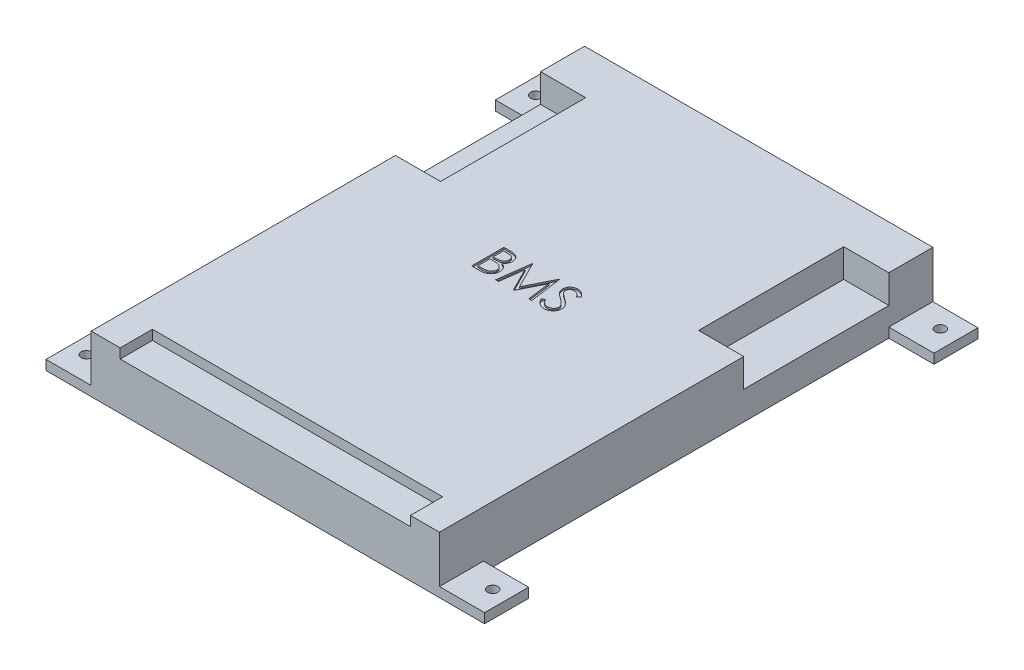
SolidWorks part; units mm, degrees
ref_plane "Front Plane" through (0, 0, 0) normal (0, 0, 1) x (1, 0, 0)
ref_plane "Top Plane" through (0, 0, 0) normal (0, 1, 0) x (1, 0, 0)
ref_plane "Right Plane" through (0, 0, 0) normal (1, 0, 0) x (0, 0, -1)
sketch "Sketch1" plane through (0, 0, 0) normal (0, 1, 0) x (1, 0, 0)
  line L0 (0, 0) -> (0, 13.65)
  line L5 (0, 13.65) -> (14, 13.65)
  line L6 (14, 13.65) -> (14, 139.35)
  line L7 (14, 139.35) -> (0, 139.35)
  line L8 (0, 139.35) -> (0, 153)
  line L9 (0, 153) -> (136, 153)
  line L10 (68, 153) -> (68, 0) construction
  line L11 (136, 0) -> (0, 0)
  line L12 (136, 139.35) -> (136, 153)
  line L13 (122, 139.35) -> (136, 139.35)
  line L14 (122, 13.65) -> (122, 139.35)
  line L15 (136, 13.65) -> (122, 13.65)
  line L16 (136, 0) -> (136, 13.65)
  line L17 (14, 76.5) -> (122, 76.5) construction
  point P18 (5, 146.85)
  point P19 (5, 7.5)
  point P20 (0, 0)
  point P21 (131, 7.5)
  point P22 (131, 146.85)
  point P23 (0, 0)
  point P24 (23.8963, 7.5)
  point P25 (0, 0)
  dimension "D1" = 153
  dimension "D2" = 125.7
  dimension "D3" = 136
  dimension "D4" = 108
  dimension "D5" = 70.35
  dimension "D6" = 126
  dimension "D7" = 139.35
extrude "Boss-Extrude1" add sketch "Sketch1" along normal blind 3
sketch "Sketch3" plane through (0, 3, 0) normal (0, 1, 0) x (1, 0, 0)
  line L0 (0, 0) -> (136, 0) construction
  line L1 (14, 0) -> (122, 0)
  line L2 (14, 0) -> (14, 153)
  line L3 (14, 153) -> (122, 153)
  line L4 (122, 0) -> (122, 153)
  line L5 (136, 153) -> (0, 153) construction
  line L6 (122, 13.65) -> (122, 139.35) construction
  line L7 (14, 139.35) -> (14, 13.65) construction
  line L8 (14, 139.35) -> (28, 139.35)
  line L9 (28, 139.35) -> (28, 94.35)
  line L10 (28, 94.35) -> (14, 94.35)
  line L11 (68, 153) -> (68, 0) construction
  line L12 (108, 94.35) -> (122, 94.35)
  line L13 (108, 139.35) -> (108, 94.35)
  line L14 (122, 139.35) -> (108, 139.35)
  line L15 (0, 139.35) -> (14, 139.35) construction
  dimension "D1" = 45
extrude "Boss-Extrude3" add sketch "Sketch3" along normal offset from surface (14.6 mm away) 17.6 contours L11 L3 L2 L8 L9 L10 L13 | L11 L1 L4 L12 L13 L14 region at (42.6509, 3, -73.1692) region at (93.3491, 3, -73.1692) up to face at (68, 0, -76.5)
extrude "Boss-Extrude4" add sketch "Sketch3<3>" along normal offset from surface (5.8 mm away) 8.8 contours L10 L9 L8 | L4 L14 L13 L12 region at (21, 3, -116.85) region at (115, 3, -116.85) up to face at (68, 0, -76.5)
sketch "Sketch3<3>" plane through (0, 3, 0) normal (0, 1, 0) x (1, 0, 0) same geometry as "Sketch3"
hole_wizard "M3 Clearance Hole1" positions "Sketch6" profile "Sketch7" hole size "M3" standard "ANSI Metric" end condition through all
sketch "Sketch6" plane through (0, 3, 0) normal (0, 1, 0) x (1, 0, 0)
  point P0 (5, 146.85)
  point P3 (130.4587, 146.8557)
  point P5 (131, 7.5)
  point P8 (5, 7.5)
sketch "Sketch7" plane through (5, 3, -146.85) normal (1, 0, 0) x (0, 0, 1)
  line L0 (0, 0) -> (0, 3)
  line L1 (0, 3) -> (1.6, 3)
  line L2 (1.6, 3) -> (1.6, 0)
  line L5 (1.6, 0) -> (0, 0)
  line L11 (0, -6.35) -> (0, 107.95) construction
  dimension "Thru Hole Dia." = 3.2
  dimension "Thru Hole Depth" = 3
sketch "Sketch2" plane through (0, 17.6, 0) normal (0, 1, 0) x (1, 0, 0)
  line L0 (14, 76.5) -> (122, 76.5) construction
  line L3 (122, 13.65) -> (122, 139.35) construction
  text T0 "BMS" font "Century Gothic" height 10
  point P2 (0, 0)
  point P3 (0, 0)
extrude "Cut-Extrude1" cut sketch "Sketch2" against normal blind 0.5
sketch "Sketch8" plane through (0, 17.6, 0) normal (0, 1, 0) x (1, 0, 0)
  line L0 (23, 10) -> (23, 0)
  line L1 (23, 10) -> (113, 10)
  line L2 (23, 0) -> (113, 0)
  line L3 (113, 10) -> (113, 0)
  line L4 (23, 10) -> (113, 0) construction
  line L5 (23, 0) -> (113, 10) construction
  line L6 (68, 153) -> (68, 0) construction
  line L7 (136, 0) -> (0, 0) construction
  point P0 (0, 0)
  point P1 (68, 5)
  dimension "D1" = 90
  dimension "D2" = 10
extrude "Cut-Extrude2" cut sketch "Sketch8" against normal blind 3
